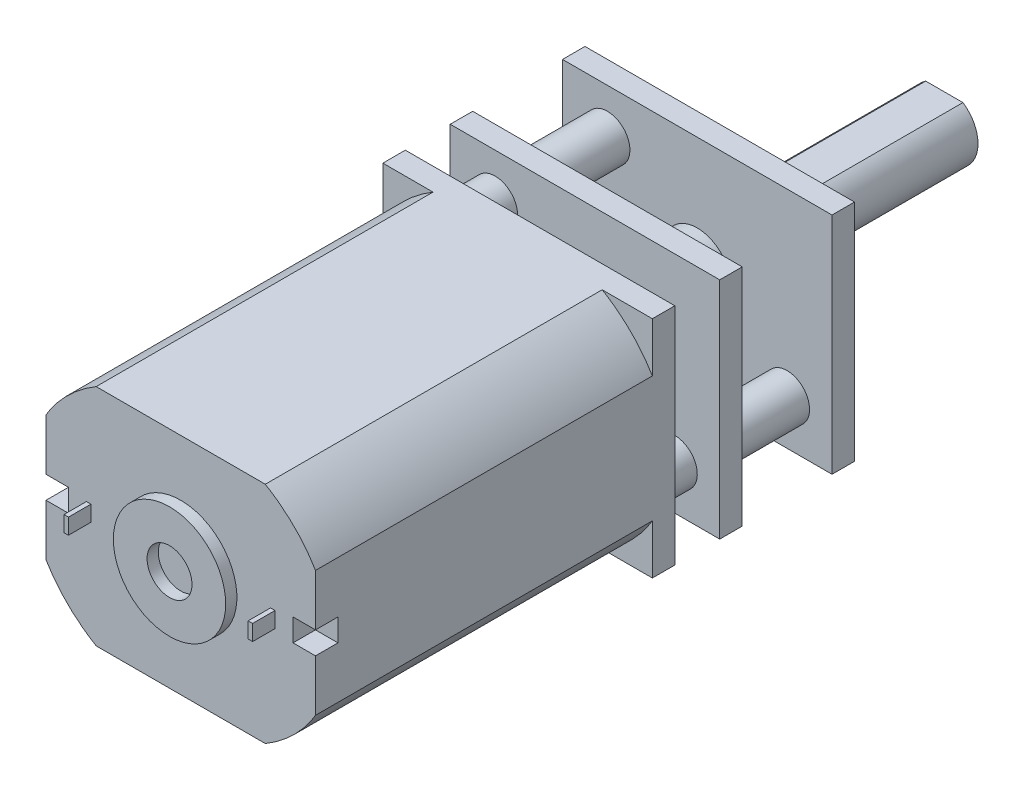
SolidWorks part; units mm, degrees
note: '?' marks a value the reader was unsure of.
material "Aleación 1060"
ref_plane "Alzado" through (0, 0, 0) normal (0, 0, 1) x (1, 0, 0)
ref_plane "Planta" through (0, 0, 0) normal (0, 1, 0) x (1, 0, 0)
ref_plane "Vista lateral" through (0, 0, 0) normal (1, 0, 0) x (0, 0, -1)
sketch "Croquis1" plane through (0, 0, 0) normal (0, 0, 1) x (1, 0, 0)
  line L1 (-6, 10) -> (6, 10)
  line L2 (-6, 10) -> (-6, 0)
  line L3 (-6, 0) -> (6, 0)
  line L4 (6, 10) -> (6, 0)
  point P4 (0, 0)
  point P8 (-6, 10)
  point P11 (6, 0)
  point P16 (6, 10)
  dimension "D1" = 12
  dimension "D2" = 10
extrude "Saliente-Extruir1" add sketch "Croquis1" along normal blind 9
sketch "Croquis2" plane through (0, 0, 0) normal (0, 0, -1) x (-1, 0, 0)
  line L0 (-10.0491, 5) -> (10.0491, 5) construction
  line L1 (0, 16.2227) -> (0, -6.2227) construction
  line L2 (6, 10) -> (6, 0) construction
  circle A0 centre (0, 5) radius 2
  circle A1 centre (0, 5) radius 1.5
  point P6 (6, 5)
  point P8 (0, 5)
  point P9 (0, 5)
  dimension "D1" = 4
  dimension "D2" = 3
extrude "Saliente-Extruir2" add sketch "Croquis2" along normal blind 1
sketch "Croquis3" plane through (0, 0, 0) normal (0, 0, -1) x (-1, 0, 0)
  circle A0 centre (0, 5) radius 1.5
  dimension "D1" = 3
extrude "Saliente-Extruir3" add sketch "Croquis3" along normal blind 10
sketch "Croquis5" plane through (0, 0, -10) normal (0, 0, -1) x (-1, 0, 0)
  line L0 (-0.8292, 6.25) -> (0.8292, 6.25)
  circle A0 centre (0, 5) radius 1.5 construction
  arc A1 (0.8292, 6.25) -> (-0.8292, 6.25) centre (0, 5) ccw
  dimension "D1" = 1.25
  dimension "D2" = 3
extrude "Cortar-Extruir1" cut sketch "Croquis5" against normal blind 8.5
sketch "Croquis6" plane through (-6, 0, 0) normal (-1, 0, 0) x (0, 0, 1)
  line L0 (9, 0) -> (0, 0) construction
  line L1 (0, 10) -> (1, 10)
  line L2 (0, 10) -> (0, 0)
  line L3 (0, 0) -> (1, 0)
  line L4 (1, 10) -> (1, 0)
  line L5 (9, 10) -> (0, 10) construction
  line L6 (5, 10) -> (6, 10)
  line L7 (5, 10) -> (5, 0)
  line L8 (5, 0) -> (6, 0)
  line L9 (6, 10) -> (6, 0)
  line L11 (8, 10) -> (9, 10)
  line L12 (8, 10) -> (8, 0)
  line L13 (8, 0) -> (9, 0)
  line L14 (9, 10) -> (9, 0)
  line M9 (0, 0) -> (9, 0)
  line M11 (9, 10) -> (0, 10)
  dimension "D1" = 1
  dimension "D2" = 1
  dimension "D3" = 1
  dimension "D4" = 2
extrude "Cortar-Extruir2" cut sketch "Croquis6" against normal through all contours L7 L4 M11 M9 | L12 L9 M11 M9
sketch "Croquis7" plane through (0, 0, 0) normal (0, 0, -1) x (-1, 0, 0)
  line L0 (-6, 0) -> (-6, 10) construction
  line L1 (6, 0) -> (-6, 0) construction
  line L2 (8.7982, 5) -> (-9.7411, 5) construction
  line L3 (6, 10) -> (6, 0) construction
  line L4 (-6, 10) -> (6, 10) construction
  circle A0 centre (-4, 2) radius 1
  circle A1 centre (4, 8) radius 1
  point P12 (6, 5)
  dimension "D1" = 2
  dimension "D2" = 2
  dimension "D3" = 2
  dimension "D4" = 2
  dimension "D9" = 2
  dimension "D10" = 2
extrude "Saliente-Extruir5" add sketch "Croquis7" against normal through all
sketch "Croquis8" plane through (0, 0, 0) normal (0, 0, -1) x (-1, 0, 0)
  line L0 (-6, 0) -> (-6, 10) construction
  line L2 (6, 0) -> (-6, 0) construction
  line L3 (6, 10) -> (6, 0) construction
  line L4 (-4, 0.453) -> (-4, 4.6433) construction
  line L5 (-4.125, 2.5) -> (-3.875, 2.5)
  line L6 (-4.125, 2.5) -> (-4.125, 1.5)
  line L7 (-4.125, 1.5) -> (-3.875, 1.5)
  line L8 (-3.875, 2.5) -> (-3.875, 1.5)
  line L9 (-3.5, 2.125) -> (-4.5, 2.125)
  line L10 (-3.5, 2.125) -> (-3.5, 1.875)
  line L11 (-3.5, 1.875) -> (-4.5, 1.875)
  line L12 (-4.5, 2.125) -> (-4.5, 1.875)
  line L13 (3.875, 8.5) -> (4.125, 8.5)
  line L14 (3.875, 8.5) -> (3.875, 7.5)
  line L15 (3.875, 7.5) -> (4.125, 7.5)
  line L16 (4.125, 8.5) -> (4.125, 7.5)
  line L17 (3.5, 8.125) -> (4.5, 8.125)
  line L18 (3.5, 8.125) -> (3.5, 7.875)
  line L19 (3.5, 7.875) -> (4.5, 7.875)
  line L20 (4.5, 8.125) -> (4.5, 7.875)
  line L21 (-0.468, 2) -> (-13.6825, 2) construction
  line L22 (4, 6.6103) -> (4, 10.6433) construction
  line L23 (2.423, 8) -> (5.9268, 8) construction
  line L24 (-6, 10) -> (6, 10) construction
  circle A0 centre (-4, 2) radius 1 construction
  circle A1 centre (4, 8) radius 1 construction
  circle A2 centre (-4, 2) radius 1
  circle A3 centre (4, 8) radius 1
  point P34 (-4, 2.5)
  point P36 (-4, 1.875)
  point P37 (-4.5, 2)
  point P38 (-3.875, 2)
  point P39 (4.125, 8)
  point P40 (4, 7.5)
  point P41 (4, 7.875)
  point P42 (3.5, 8)
  dimension "D1" = 2
  dimension "D2" = 2
  dimension "D5" = 2
  dimension "D3" = 2
  dimension "D4" = 2
  dimension "D6" = 2
  dimension "D7" = 0.25
  dimension "D8" = 1
  dimension "D9" = 1
  dimension "D10" = 0.25
  dimension "D11" = 0.25
  dimension "D12" = 1
  dimension "D13" = 0.25
  dimension "D14" = 1
extrude "Cortar-Extruir3" cut sketch "Croquis8" against normal blind 1 draft 22 contours L8 L11 L6 L7 | L9 L12 L11 L6 | L11 L8 L9 L6 | L9 L8 L5 L6 | L11 L10 L9 L8 | L14 L17 L16 L13 | L20 L17 L16 L19 | L18 L19 L14 L17 | L14 L19 L16 L17 | L19 L14 L15 L16
sketch "Croquis9" plane through (0, 0, 0) normal (0, 0, -1) x (-1, 0, 0)
  line L0 (-6, 0) -> (-6, 10) construction
  line L1 (6, 0) -> (-6, 0) construction
  line L2 (6, 10) -> (6, 0) construction
  line L3 (-6, 10) -> (6, 10) construction
  circle A0 centre (-4, 2) radius 1
  circle A1 centre (4, 8) radius 1
  dimension "D1" = 2
  dimension "D2" = 2
  dimension "D3" = 2
  dimension "D4" = 2
  dimension "D5" = 2
  dimension "D6" = 2
extrude "Cortar-Extruir4" cut sketch "Croquis9" against normal blind 0.1
sketch "Croquis10" plane through (0, 0, 9) normal (0, 0, 1) x (1, 0, 0)
  line L1 (-5.9, 10) -> (5.9, 10)
  line L2 (-6, 9.9) -> (-6, 0.1)
  line L3 (-5.9, 0) -> (5.9, 0)
  line L4 (6, 9.9) -> (6, 0.1)
  arc A0 (-6, 9.9) -> (-5.9, 10) centre (-5.9, 9.9) cw
  arc A1 (6, 9.9) -> (5.9, 10) centre (5.9, 9.9) ccw
  arc A2 (-6, 0.1) -> (-5.9, 0) centre (-5.9, 0.1) ccw
  arc A3 (6, 0.1) -> (5.9, 0) centre (5.9, 0.1) cw
  point P8 (-6, 10)
  point P15 (6, 0)
  dimension "D1" = 0.1
  dimension "D2" = 0.1
  dimension "D3" = 0.1
  dimension "D4" = 0.1
extrude "Saliente-Extruir7" add sketch "Croquis10" along normal blind 15
sketch "Croquis11" plane through (0, 0, 24) normal (0, 0, 1) x (1, 0, 0)
  line L0 (-8.7536, 5) -> (8.7536, 5) construction
  line L1 (6, 0.1) -> (6, 9.9) construction
  point P2 (0, 5)
  point P7 (6, 5)
sketch "Croquis12" plane through (0, 0, 24) normal (0, 0, 1) x (1, 0, 0)
  line L0 (-8.7536, 5) -> (8.7536, 5) construction
  ellipse E0 centre (0, 5) end of major axis (-6.7757, 5) minor radius 6.0146
  arc M2 (-5.9, 10) -> (-6, 9.9) centre (-5.9, 9.9) ccw
  line M3 (-6, 9.9) -> (-6, 0.1)
  arc M4 (-6, 0.1) -> (-5.9, 0) centre (-5.9, 0.1) ccw
  line M5 (-5.9, 0) -> (5.9, 0)
  arc M6 (5.9, 0) -> (6, 0.1) centre (5.9, 0.1) ccw
  line M7 (6, 0.1) -> (6, 9.9)
  arc M8 (6, 9.9) -> (5.9, 10) centre (5.9, 9.9) ccw
  line M9 (5.9, 10) -> (-5.9, 10)
  dimension "D1" = 6.7757
  dimension "D2" = 6.0146
extrude "Cortar-Extruir6" cut sketch "Croquis12" against normal blind 15 contours E0 M9 M2 M3 | E0 M7 M8 M9 | E0 M5 M6 M7 | E0 M3 M4 M5
sketch "Croquis14" plane through (0, 0, 1) normal (0, 0, 1) x (1, 0, 0)
  line L0 (-8.7536, 5) -> (8.7536, 5) construction
  circle A0 centre (0, 5) radius 1.5
  dimension "D1" = 3
extrude "Saliente-Extruir9" add sketch "Croquis14" along normal blind 10
sketch "Croquis15" plane through (-6, 0, 0) normal (-1, 0, 0) x (0, 0, 1)
  line L0 (24, 5) -> (20.444, 5) construction
  line L1 (23, 5.5) -> (24, 5.5)
  line L2 (23, 5.5) -> (23, 4.5)
  line L3 (23, 4.5) -> (24, 4.5)
  line L4 (24, 5.5) -> (24, 4.5)
  line L5 (24, 7.7945) -> (24, 2.2055) construction
  point P8 (24, 5)
  dimension "D1" = 1
  dimension "D2" = 1
extrude "Cortar-Extruir7" cut sketch "Croquis15" against normal blind 1
mirror "Simetría1" about plane through (0, 0, 0) normal (1, 0, 0) of "Cortar-Extruir7"
sketch "Croquis16" plane through (0, 0, 24) normal (0, 0, 1) x (1, 0, 0)
  line L0 (-8.7536, 5) -> (8.7536, 5) construction
  circle A0 centre (0, 5) radius 2.5
  circle A1 centre (0, 5) radius 1
  dimension "D1" = 5
  dimension "D2" = 2
extrude "Saliente-Extruir11" add sketch "Croquis16" along normal blind 0.5
sketch "Croquis17" plane through (0, 0, 24) normal (0, 0, 1) x (1, 0, 0)
  line L0 (-8.7536, 5) -> (8.7536, 5) construction
  line L1 (-4.2, 5.35) -> (-4, 5.35)
  line L2 (-4.2, 5.35) -> (-4.2, 4.65)
  line L3 (-4.2, 4.65) -> (-4, 4.65)
  line L4 (-4, 5.35) -> (-4, 4.65)
  line L5 (4, 5.35) -> (4.2, 5.35)
  line L6 (4, 5.35) -> (4, 4.65)
  line L7 (4, 4.65) -> (4.2, 4.65)
  line L8 (4.2, 5.35) -> (4.2, 4.65)
  point P8 (-4, 5)
  point P11 (4.2, 5)
  dimension "D1" = 0.7
  dimension "D2" = 0.7
  dimension "D3" = 0.2
  dimension "D4" = 0.2
  dimension "D5" = 8
extrude "Saliente-Extruir12" add sketch "Croquis17" along normal blind 1
ref_axis "Eje1" through (0, 5, -13.0512) along (0, 0, 1)?
